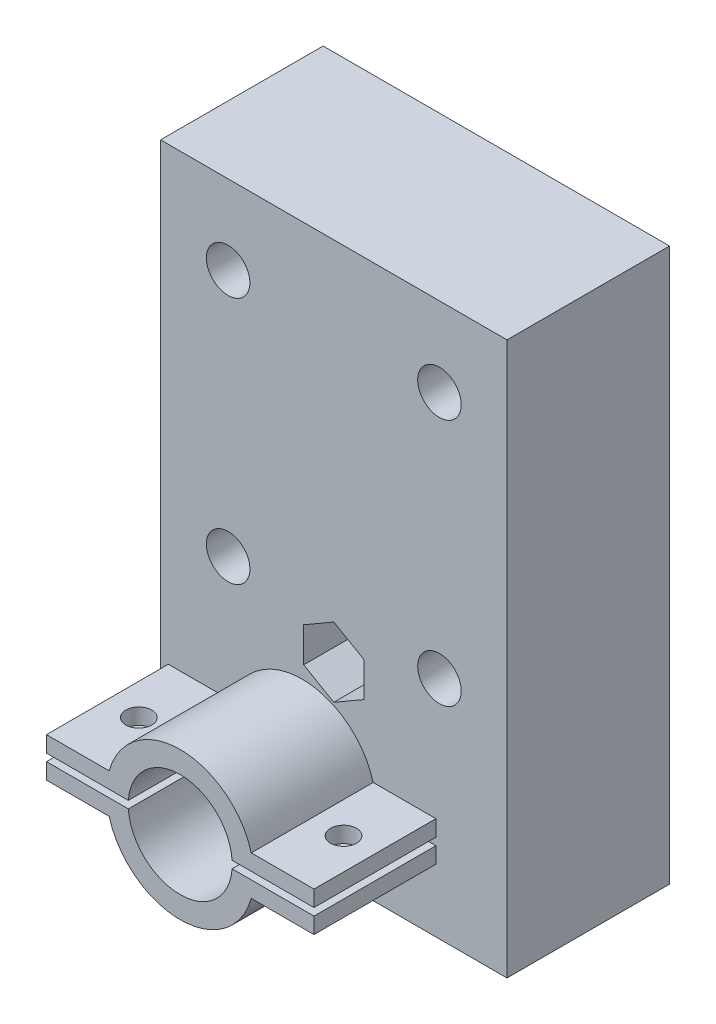
SolidWorks part; units mm, degrees
ref_plane "Front Plane" through (0, 0, 0) normal (0, 0, 1) x (1, 0, 0)
ref_plane "Top Plane" through (0, 0, 0) normal (0, 1, 0) x (1, 0, 0)
ref_plane "Right Plane" through (0, 0, 0) normal (1, 0, 0) x (0, 0, -1)
sketch "Sketch1" plane through (0, 0, 0) normal (0, 0, 1) x (1, 0, 0)
  line L0 (0, 25) -> (0, -25) construction
  line L1 (21.3115, 25) -> (-21.3115, 25)
  line L2 (21.3115, 25) -> (21.3115, -25)
  line L3 (21.3115, -25) -> (-21.3115, -25)
  line L4 (-21.3115, 25) -> (-21.3115, -25)
  line L5 (21.3115, 25) -> (-21.3115, -25) construction
  line L6 (21.3115, -25) -> (-21.3115, 25) construction
  line L7 (-21.3115, 0) -> (21.3115, 0) construction
  circle A0 centre (-13, -15.25) radius 2.677
  circle A1 centre (13, -15.25) radius 2.677
  circle A2 centre (13, 15.25) radius 2.677
  circle A3 centre (-13, 15.25) radius 2.677
  point P0 (0, 0)
  dimension "D1" = 30.5
  dimension "D2" = 26
  dimension "D3" = 50
extrude "Boss-Extrude1" add sketch "Sketch1" along normal blind 20
sketch "Sketch2" plane through (0, 0, 0) normal (0, 0, 1) x (1, 0, 0)
  circle A0 centre (0, 0) radius 8.73
  dimension "D1" = 17.46
extrude "Cut-Extrude2" cut sketch "Sketch2" along normal blind 7.94
sketch "Sketch3" plane through (0, 0, 0) normal (0, 0, -1) x (-1, 0, 0)
  circle A0 centre (0, -20) radius 2.2
  dimension "D1" = 4.4
  dimension "D2" = 20
extrude "Cut-Extrude3" cut sketch "Sketch3" against normal blind 10
sketch "Sketch5" plane through (0, 0, 0) normal (0, 0, -1) x (-1, 0, 0)
  line L1 (0, -15.7276) -> (-3.7, -17.8638)
  line L2 (-3.7, -17.8638) -> (-3.7, -22.1362)
  line L3 (-3.7, -22.1362) -> (0, -24.2724)
  line L4 (0, -24.2724) -> (3.7, -22.1362)
  line L5 (3.7, -22.1362) -> (3.7, -17.8638)
  line L6 (3.7, -17.8638) -> (0, -15.7276)
  circle A0 centre (0, -20) radius 3.7 construction
  dimension "D1" = 3.7
extrude "Cut-Extrude4" cut sketch "Sketch5" against normal through all from offset 7 offset against normal yes
sketch "Sketch6" plane through (0, 0, 0) normal (0, 0, -1) x (-1, 0, 0)
  circle A1 centre (3.8969, -32.824) radius 6.4
sketch "Sketch7" plane through (0, -25, 0) normal (0, -1, 0) x (1, 0, 0)
  line L1 (-21.3115, 20) -> (21.3115, 20)
  line L2 (-21.3115, 20) -> (-21.3115, 0)
  line L3 (-21.3115, 0) -> (21.3115, 0)
  line L4 (21.3115, 20) -> (21.3115, 0)
extrude "Boss-Extrude2" add sketch "Sketch7" along normal blind 18
extrude "Cut-Extrude5" cut sketch "Sketch6" against normal through all contours A1
sketch "Sketch8" plane through (0, 0, 20) normal (0, 0, 1) x (1, 0, 0)
  line L8 (2.487, -32.3693) -> (10.2737, -32.3693)
  line L10 (-20.3552, -31.924) -> (-20.3552, -32.3693)
  line L12 (12.5615, -31.924) -> (12.5615, -32.3693)
  line L13 (10.2737, -32.3693) -> (12.5615, -32.3693)
  line L15 (-18.0674, -32.3693) -> (-10.2807, -32.3693)
  line L17 (-18.0674, -33.2788) -> (-10.2807, -33.2788)
  line L19 (12.5615, -33.2788) -> (10.2737, -33.2788)
  line L20 (12.5615, -33.2788) -> (12.5615, -33.724)
  line L23 (-18.0674, -32.3693) -> (-20.3552, -32.3693)
  line L25 (-20.3552, -33.2788) -> (-18.0674, -33.2788)
  line L26 (-20.3552, -33.2788) -> (-20.3552, -33.724)
  line L27 (2.487, -33.2788) -> (10.2737, -33.2788)
  line L30 (-20.3552, -31.3876) -> (-20.3552, -32.3693)
  line L32 (12.5615, -31.3876) -> (12.5615, -32.3693)
  line L33 (-20.3552, -33.2788) -> (-20.3552, -34.2605)
  line L35 (12.5615, -33.2788) -> (12.5615, -34.2605)
  line L36 (-20.3552, -32.3693) -> (-20.3552, -30.3993)
  line L37 (-20.3552, -30.3993) -> (-12.6396, -30.3993)
  line L38 (-20.3552, -33.2788) -> (-20.3552, -35.2488)
  line L39 (-20.3552, -35.2488) -> (-12.6396, -35.2488)
  line L40 (12.5615, -32.3693) -> (12.5615, -30.3993)
  line L41 (12.5615, -30.3993) -> (4.8459, -30.3993)
  line L42 (12.5615, -33.2788) -> (12.5615, -35.2488)
  line L43 (12.5615, -35.2488) -> (4.8459, -35.2488)
  arc A0 (4.8459, -30.3993) -> (-12.6396, -30.3993) centre (-3.8969, -32.824) ccw
  arc A3 (-12.6396, -35.2488) -> (4.8459, -35.2488) centre (-3.8969, -32.824) ccw
  arc A7 (-12.6396, -35.2488) -> (5.0615, -34.2605) centre (-3.8969, -32.824) ccw
  arc A9 (4.8459, -30.3993) -> (-12.6396, -30.3993) centre (-3.8969, -32.824) ccw
  arc A11 (-10.2807, -33.2788) -> (2.487, -33.2788) centre (-3.8969, -32.824) ccw
  arc A12 (2.487, -32.3693) -> (-10.2807, -32.3693) centre (-3.8969, -32.824) ccw
  dimension "D2" = 1.8
extrude "Boss-Extrude5" add sketch "Sketch8" along normal blind 15 contours A9 A0 L10 A7 A3 L12 L27 L17 L15 L8 | A7 A3 L20 L19 L27 L17 L25 L26 region at (-3.8969, -26.0838, 20) region at (-14.174, -33.6191, 20)
sketch "Sketch10" plane through (0, -43, 0) normal (0, -1, 0) x (1, 0, 0)
  line L0 (21.3115, 20) -> (-21.3115, 20) construction
  line L1 (-20.3552, 35) -> (-20.3552, 20) construction
  line L4 (12.5615, 35) -> (12.5615, 20) construction
  circle A0 centre (-16.4952, 27.5) radius 1.6
  circle A1 centre (8.7015, 27.5) radius 1.6
  dimension "D1" = 7.5
  dimension "D3" = 3.86
  dimension "D2" = 3.86
extrude "Cut-Extrude8" cut sketch "Sketch10" against normal through all
